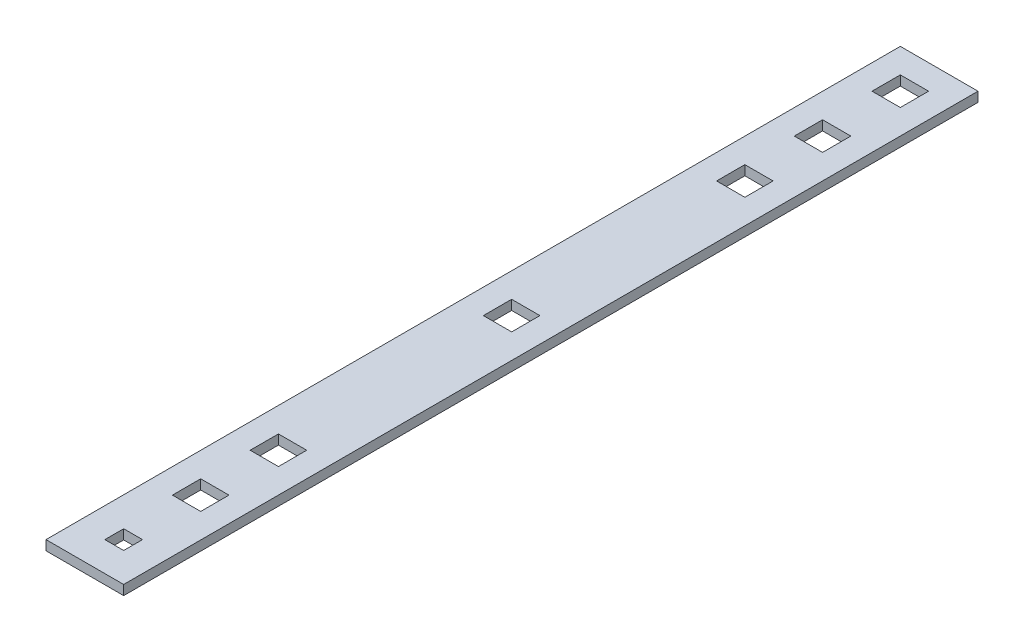
SolidWorks part; units mm, degrees
ref_plane "Front Plane" through (0, 0, 0) normal (0, 0, 1) x (1, 0, 0)
ref_plane "Top Plane" through (0, 0, 0) normal (0, 1, 0) x (1, 0, 0)
ref_plane "Right Plane" through (0, 0, 0) normal (1, 0, 0) x (0, 0, -1)
sketch "Sketch1" plane through (0, 0, 0) normal (0, 1, 0) x (1, 0, 0)
  line L1 (-0.0371, 101.5375) -> (12.6629, 101.5375)
  line L2 (-0.0371, 101.5375) -> (-0.0371, -38.1625)
  line L3 (-0.0371, -38.1625) -> (12.6629, -38.1625)
  line L4 (12.6629, 101.5375) -> (12.6629, -38.1625)
  line L5 (4.0001, 97.4975) -> (8.6229, 97.4975)
  line L6 (4.0001, 97.4975) -> (4.0001, 92.8747)
  line L7 (4.0001, 92.8747) -> (8.6229, 92.8747)
  line L8 (8.6229, 97.4975) -> (8.6229, 92.8747)
  line L40 (4.0001, 84.7863) -> (4.0001, 80.1635)
  line L41 (4.0001, 84.7863) -> (8.6229, 84.7863)
  line L42 (8.6229, 84.7863) -> (8.6229, 80.1635)
  line L43 (4.0001, 80.1635) -> (8.6229, 80.1635)
  line L44 (4.0001, 72.075) -> (4.0001, 67.4522)
  line L45 (4.0001, 72.075) -> (8.6229, 72.075)
  line L46 (8.6229, 72.075) -> (8.6229, 67.4522)
  line L47 (4.0001, 67.4522) -> (8.6229, 67.4522)
  line L49 (4.7729, -30.2725) -> (7.8529, -30.2725)
  line L50 (4.7729, -30.2725) -> (4.7729, -33.3525)
  line L51 (4.7729, -33.3525) -> (7.8529, -33.3525)
  line L52 (7.8529, -30.2725) -> (7.8529, -33.3525)
  line L60 (4.0001, 33.9411) -> (4.0001, 29.3183)
  line L61 (4.0001, 33.9411) -> (8.6229, 33.9411)
  line L62 (8.6229, 33.9411) -> (8.6229, 29.3183)
  line L63 (4.0001, 29.3183) -> (8.6229, 29.3183)
  line L72 (4.0001, -4.1927) -> (4.0001, -8.8155)
  line L73 (4.0001, -4.1927) -> (8.6229, -4.1927)
  line L74 (8.6229, -4.1927) -> (8.6229, -8.8155)
  line L75 (4.0001, -8.8155) -> (8.6229, -8.8155)
  line L76 (4.0001, -16.904) -> (4.0001, -21.5268)
  line L77 (4.0001, -16.904) -> (8.6229, -16.904)
  line L78 (8.6229, -16.904) -> (8.6229, -21.5268)
  line L79 (4.0001, -21.5268) -> (8.6229, -21.5268)
  line L80 (4.0001, 46.6524) -> (4.0001, 42.0296) [skipped]
  line L81 (4.0001, 42.0296) -> (8.6229, 42.0296) [skipped]
  line L82 (8.6229, 46.6524) -> (8.6229, 42.0296) [skipped]
  line L83 (4.0001, 46.6524) -> (8.6229, 46.6524) [skipped]
  line L84 (4.0001, 59.3637) -> (4.0001, 54.7409) [skipped]
  line L85 (4.0001, 54.7409) -> (8.6229, 54.7409) [skipped]
  line L86 (8.6229, 59.3637) -> (8.6229, 54.7409) [skipped]
  line L87 (4.0001, 59.3637) -> (8.6229, 59.3637) [skipped]
  line L88 (4.0001, 21.2299) -> (4.0001, 16.6071) [skipped]
  line L89 (4.0001, 16.6071) -> (8.6229, 16.6071) [skipped]
  line L90 (8.6229, 21.2299) -> (8.6229, 16.6071) [skipped]
  line L91 (4.0001, 21.2299) -> (8.6229, 21.2299) [skipped]
  line L92 (4.0001, 8.5186) -> (4.0001, 3.8958) [skipped]
  line L93 (4.0001, 3.8958) -> (8.6229, 3.8958) [skipped]
  line L94 (8.6229, 8.5186) -> (8.6229, 3.8958) [skipped]
  line L95 (4.0001, 8.5186) -> (8.6229, 8.5186) [skipped]
  point P8 (6.3129, 101.5375)
  dimension "D1" = 12.7
  dimension "D2" = 139.7
  dimension "D3" = 4.6228
  dimension "D4" = 4.6228
  dimension "D5" = 4.04
  dimension "D6" = 4.04
  dimension "D8" = 3.08
  dimension "D9" = 3.08
  dimension "D10" = 4.81
  dimension "D11" = 4.81
  dimension "D7" = 10
extrude "Boss-Extrude1" add sketch "Sketch1" along normal blind 1.5875
